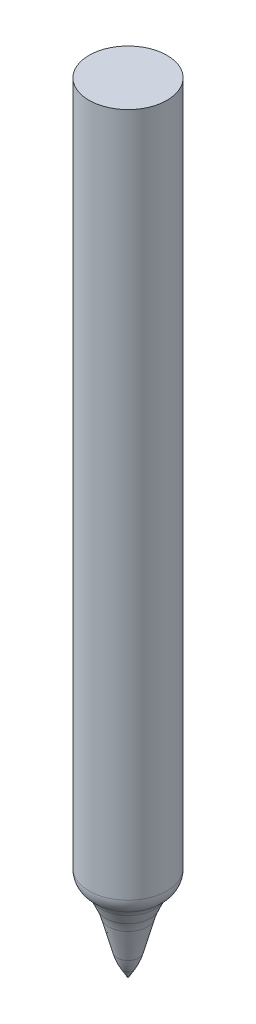
SolidWorks part; units mm, degrees
ref_plane "Front Plane" through (0, 0, 0) normal (0, 0, 1) x (1, 0, 0)
ref_plane "Top Plane" through (0, 0, 0) normal (0, 1, 0) x (1, 0, 0)
ref_plane "Right Plane" through (0, 0, 0) normal (1, 0, 0) x (0, 0, -1)
sketch "Sketch1" plane through (0, 0, 0) normal (0, 0, 1) x (1, 0, 0)
  line L0 (1.1547, 2) -> (2.6606, 7.62)
  line L1 (0, 0) -> (5.08, 0)
  line L2 (0, 0) -> (0, 101.6)
  line L3 (0, 101.6) -> (5.08, 101.6)
  line L4 (5.08, 0) -> (5.08, 101.6)
  line L5 (1.1547, 2) -> (0, 0)
  line L6 (2.6606, 7.62) -> (3.81, 10.16)
  line L7 (3.81, 10.16) -> (5.08, 10.16)
  dimension "D2" = 5.08
  dimension "D1" = 60
  dimension "D4" = 2
  dimension "D5" = 101.6
  dimension "D3" = 75
  dimension "D7" = 1.27
  dimension "D6" = 10.16
  dimension "D8" = 7.62
revolve "Revolve1" add sketch "Sketch1" angle 360 about L2 region at (2.4855, 53.8328, 0)
fillet "Fillet1" radius 2.54 1 edges at (0, 10.16, -5.08)
fillet "Fillet2" radius 2.54 1 edges at (0, 10.16, -3.81)
fillet "Fillet3" radius 7.62 2 edges at (0, 2, -1.1547) (0, 7.62, -2.6606)
equation "\"diamiter\"= 0.2045in * 2"
equation "\"D2@Sketch1\"=\"diamiter\"/2"
